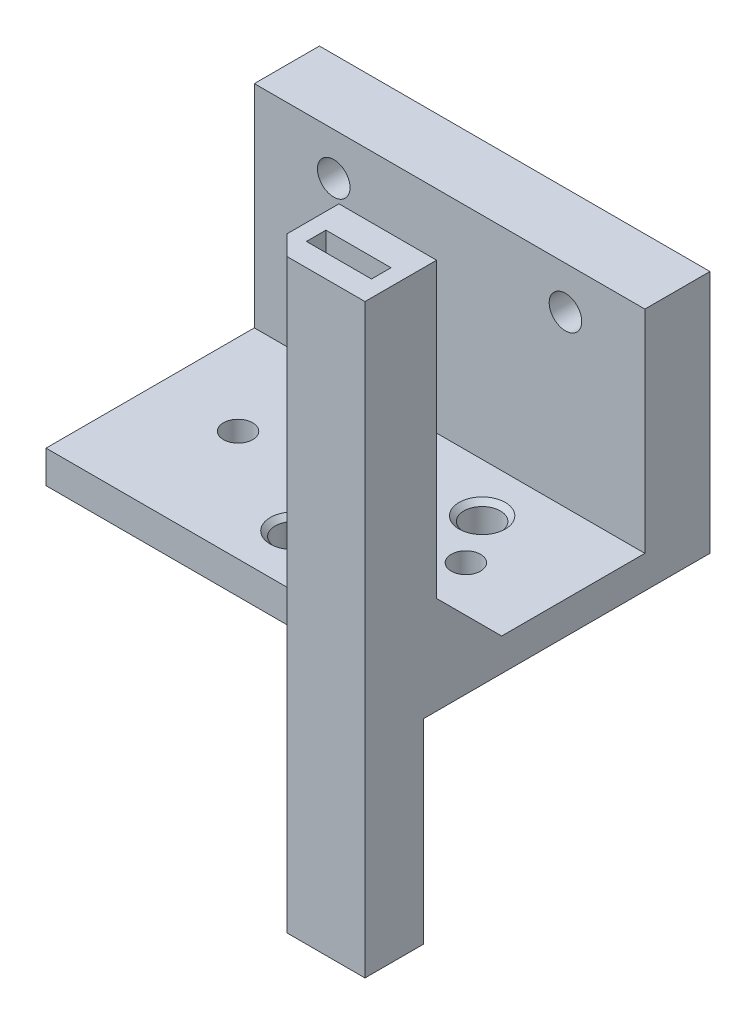
SolidWorks part; units mm, degrees
material "PET"
ref_plane "Front Plane" through (0, 0, 0) normal (0, 0, 1) x (1, 0, 0)
ref_plane "Top Plane" through (0, 0, 0) normal (0, 1, 0) x (1, 0, 0)
ref_plane "Right Plane" through (0, 0, 0) normal (1, 0, 0) x (0, 0, -1)
sketch "Sketch1" plane through (0, 0, 0) normal (0, 1, 0) x (1, 0, 0)
  line L0 (-30, 15) -> (30, 15) construction
  line L2 (-30, 0) -> (-30, 40)
  line L3 (-30, 40) -> (30, 40)
  line L4 (30, 0) -> (30, 40)
  line L5 (0, 0) -> (30, 40) construction
  line L6 (-30, 40) -> (0, 0) construction
  line L7 (-30, 22.5) -> (30, 22.5) construction
  line L8 (-30, 0) -> (-30, -2)
  line L11 (-30, -2) -> (30, -2)
  line L12 (30, -2) -> (30, 0)
  line L13 (-30, 0) -> (30, 0) construction
  line L14 (0, 0) -> (0, 27.8808) construction
  circle A0 centre (-12.5, 22.5) radius 2.8
  circle A1 centre (12.5, 22.5) radius 2.8
  circle A3 centre (-17.5, 15) radius 2.25
  circle A4 centre (17.5, 15) radius 2.25
  circle A6 centre (0, 6) radius 2.8
  point P0 (0, 0)
  dimension "D6" = 5.6
  dimension "D7" = 5.6
  dimension "D8" = 4.5
  dimension "D9" = 4.5
  dimension "D5" = 5.6
  dimension "D2" = 60
  dimension "D4" = 17.5
  dimension "D10" = 12.5
  dimension "D11" = 12.5
  dimension "D12" = 25
  dimension "D17" = 40
  dimension "D18" = 30
  dimension "D20" = 17.5
  dimension "D21" = 17.5
  dimension "D3" = 2
  dimension "D13" = 6
extrude "Boss-Extrude1" add sketch "Sketch1" along normal blind 5
sketch "Sketch3" plane through (0, 5, 0) normal (0, 1, 0) x (1, 0, 0)
  line L2 (-30, 40) -> (-30, 30)
  line L3 (-30, 30) -> (30, 30)
  line L5 (30, 40) -> (-30, 40)
  line L6 (30, 40) -> (30, 30)
  dimension "D2" = 10
extrude "Boss-Extrude3" add sketch "Sketch3" along normal blind 32.5
sketch "Sketch4" plane through (0, 0, -40) normal (0, 0, -1) x (-1, 0, 0)
  line L0 (-30, 0) -> (30, 0) construction
  line L2 (-17.8, 31) -> (17.8, 31) construction
  circle A0 centre (-17.8, 31) radius 2.5
  circle A1 centre (17.8, 31) radius 2.5
  dimension "D3" = 5
  dimension "D4" = 5
  dimension "D1" = 17.8
  dimension "D2" = 35.6
  dimension "D5" = 31
extrude "Cut-Extrude1" cut sketch "Sketch4" against normal through all
chamfer "Chamfer1" distance 0.75 angle 45 3 edges at (-12.5, 5, -19.7) (12.5, 5, -19.7) (0, 5, -3.2)
sketch "Sketch5" plane through (0, 0, 0) normal (0, -1, 0) x (1, 0, 0)
  line L0 (18, 13) -> (15, 10)
  line L1 (30, 2) -> (15, 2)
  line L2 (30, 2) -> (30, 13)
  line L3 (30, 13) -> (18, 13)
  line L6 (15, 2) -> (15, 10)
  line L7 (27.5, 9.5) -> (17.5, 9.5)
  line L8 (27.5, 9.5) -> (27.5, 6.5)
  line L9 (27.5, 6.5) -> (17.5, 6.5)
  line L10 (17.5, 9.5) -> (17.5, 6.5)
  dimension "D1" = 11
  dimension "D2" = 12
  dimension "D3" = 10
  dimension "D4" = 2.5
  dimension "D5" = 3
  dimension "D6" = 4.5
  dimension "D7" = 15
  dimension "D8" = 135
extrude "Boss-Extrude4" add sketch "Sketch5" along normal blind 30 and the other way blind 60
chamfer "Chamfer2" distance 10 angle 45 1 edges at (22.5, 5, 2)
chamfer "Chamfer3" distance 5 angle 45 2 edges at (15, 5, -3) (15, 2.5, 2)
sketch "Sketch7" plane through (30, 0, 0) normal (1, 0, 0) x (0, 0, -1)
  line L0 (-2, -30) -> (-13, -30) construction
  line L1 (-2, 0) -> (-4, 0)
  line L2 (-2, 0) -> (-2, -30)
  line L3 (-2, -30) -> (-4, -30)
  line L4 (-4, 0) -> (-4, -30)
  dimension "D1" = 2
extrude "Cut-Extrude2" cut sketch "Sketch7" against normal through all
sketch "Sketch8" plane through (30, 0, 0) normal (1, 0, 0) x (0, 0, -1)
  line L0 (30, 37.5) -> (-2, 37.5)
  line L1 (-2, 60) -> (-2, 15) construction
  line L2 (-2, 37.5) -> (-2, 15)
  line L3 (-2, 15) -> (8, 5)
  line L4 (8, 5) -> (30, 5)
  line L5 (30, 5) -> (30, 37.5)
extrude "Boss-Extrude5" add sketch "Sketch8" against normal blind 5
sketch "Sketch9" plane through (25, 0, 0) normal (-1, 0, 0) x (0, 0, 1)
  line L0 (-30, 37.5) -> (-30, 5)
  line L1 (-30, 5) -> (-8, 5)
  line L2 (-8, 5) -> (2, 15)
  line L3 (2, 15) -> (2, 37.5)
  line L4 (2, 60) -> (2, 15) construction
  line L5 (2, 37.5) -> (-30, 37.5)
extrude "Cut-Extrude3" cut sketch "Sketch9" against normal through all
equation "\"D18@Sketch1\"=\"D2@Sketch1\"/2"
equation "\"D1@Sketch4\"=\"D2@Sketch4\"/2"
